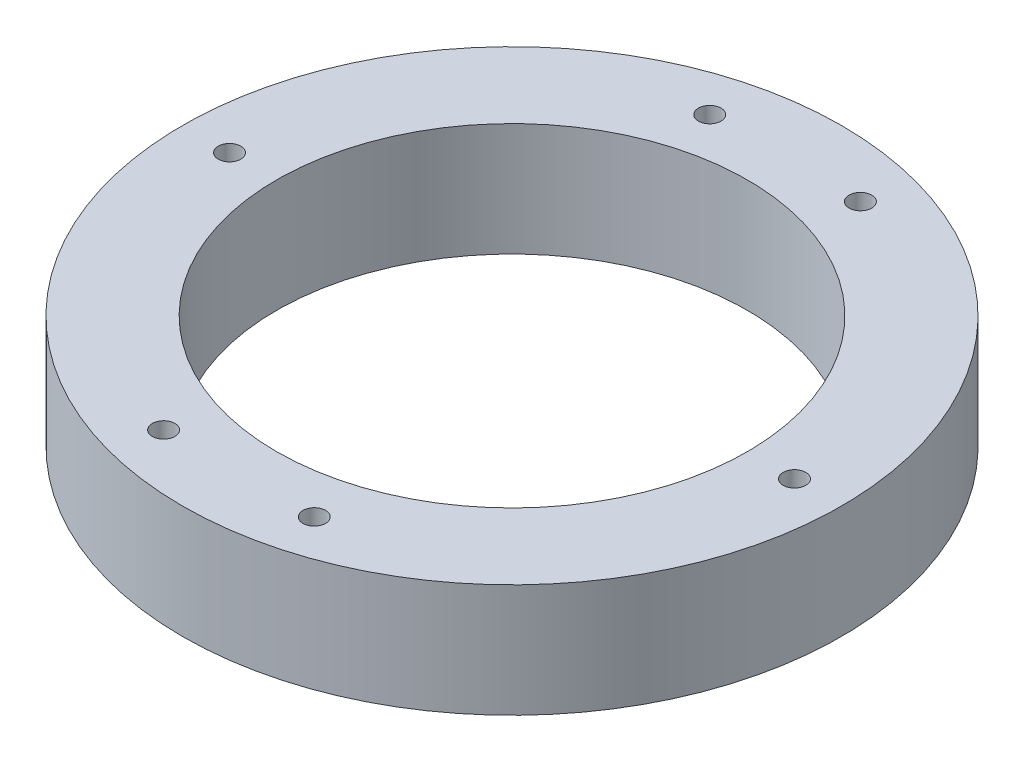
SolidWorks part; units mm, degrees
ref_plane "Спереди" through (0, 0, 0) normal (0, 0, 1) x (1, 0, 0)
ref_plane "Сверху" through (0, 0, 0) normal (0, 1, 0) x (1, 0, 0)
ref_plane "Справа" through (0, 0, 0) normal (1, 0, 0) x (0, 0, -1)
sketch "Sketch1" plane through (0, 0, 0) normal (0, 1, 0) x (1, 0, 0)
  line L0 (-11.7247, 0) -> (16.8046, 0) construction
  line L1 (0, 7.3106) -> (0, -15.7423) construction
  circle A0 centre (0, 0) radius 17.5
  circle A1 centre (-4, 14.5) radius 0.6
  circle A2 centre (-4, -14.5) radius 0.6
  circle A3 centre (15, 0) radius 0.6
  circle A4 centre (-15, 0) radius 0.6
  circle A5 centre (4, 14.5) radius 0.6
  circle A6 centre (4, -14.5) radius 0.6
  circle A8 centre (0, 0) radius 12.5
  dimension "D1" = 35
  dimension "D7" = 1.2
  dimension "D8" = 1.2
  dimension "D9" = 1.2
  dimension "D10" = 1.2
  dimension "D11" = 1.2
  dimension "D12" = 1.2
  dimension "D18" = 25
  dimension "D2" = 15
  dimension "D3" = 4
  dimension "D4" = 14.5
  dimension "D5" = 14.5
  dimension "D6" = 4
  dimension "D13" = 15
  dimension "D14" = 4
  dimension "D15" = 14.5
  dimension "D16" = 14.5
  dimension "D17" = 4
extrude "Boss-Extrude1" add sketch "Sketch1" along normal blind 6
